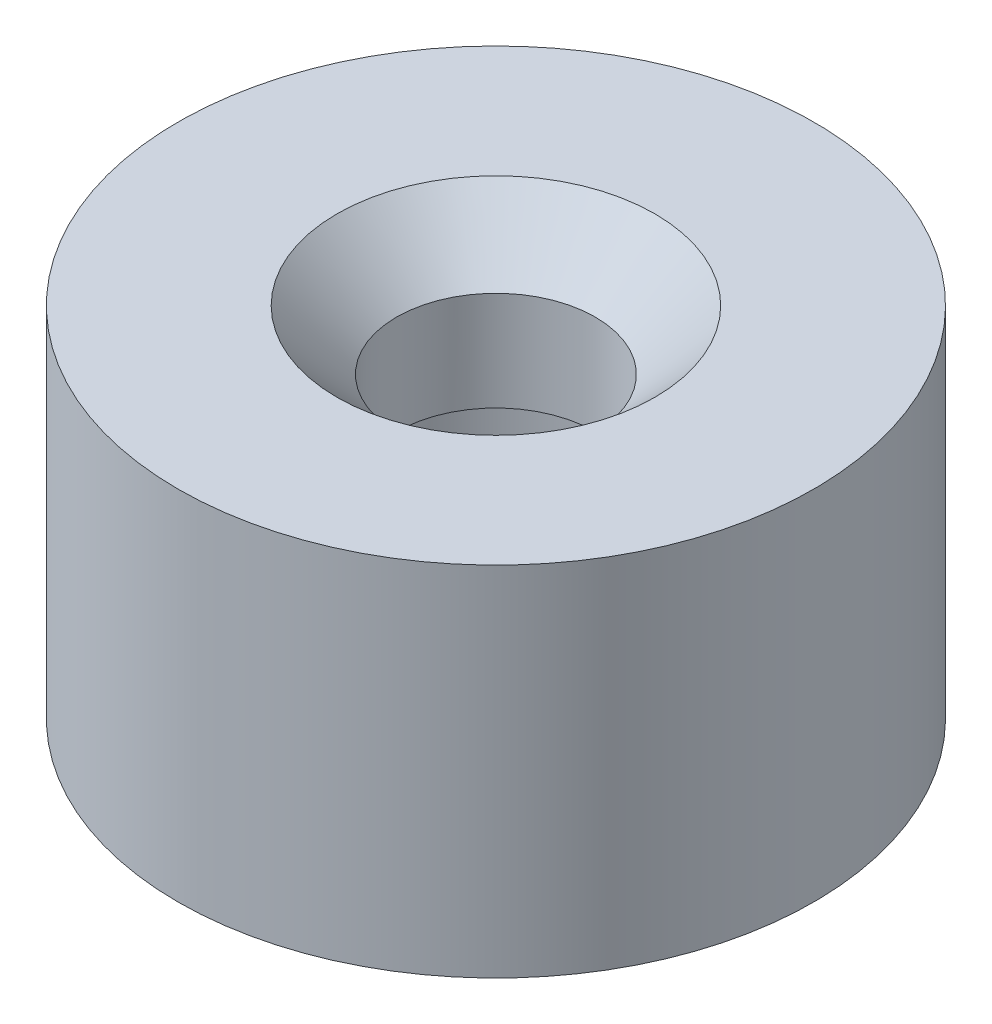
SolidWorks part; units mm, degrees
ref_plane "Front Plane" through (0, 0, 0) normal (0, 0, 1) x (1, 0, 0)
ref_plane "Top Plane" through (0, 0, 0) normal (0, 1, 0) x (1, 0, 0)
ref_plane "Right Plane" through (0, 0, 0) normal (1, 0, 0) x (0, 0, -1)
sketch "Sketch1" plane through (0, 0, 0) normal (0, 1, 0) x (1, 0, 0)
  circle A0 centre (0, 0) radius 8
  circle A1 centre (0, 0) radius 2.5
  dimension "D1" = 16
  dimension "D2" = 5
extrude "Boss-Extrude1" add sketch "Sketch1" along normal blind 9
sketch "Sketch2" plane through (0, 9, 0) normal (0, 1, 0) x (1, 0, 0)
  circle A0 centre (0, 0) radius 4
  circle A1 centre (0, 0) radius 2.5 construction
  dimension "D1" = 8
extrude "Cut-Extrude1" cut sketch "Sketch2" against normal blind 2 draft 45
sketch "Sketch3" plane through (0, 0, 0) normal (0, -1, 0) x (-1, 0, 0)
  circle A0 centre (0, 0) radius 4
  circle A1 centre (0, 0) radius 2.5 construction
  dimension "D1" = 8
extrude "Cut-Extrude2" cut sketch "Sketch3" against normal blind 5
